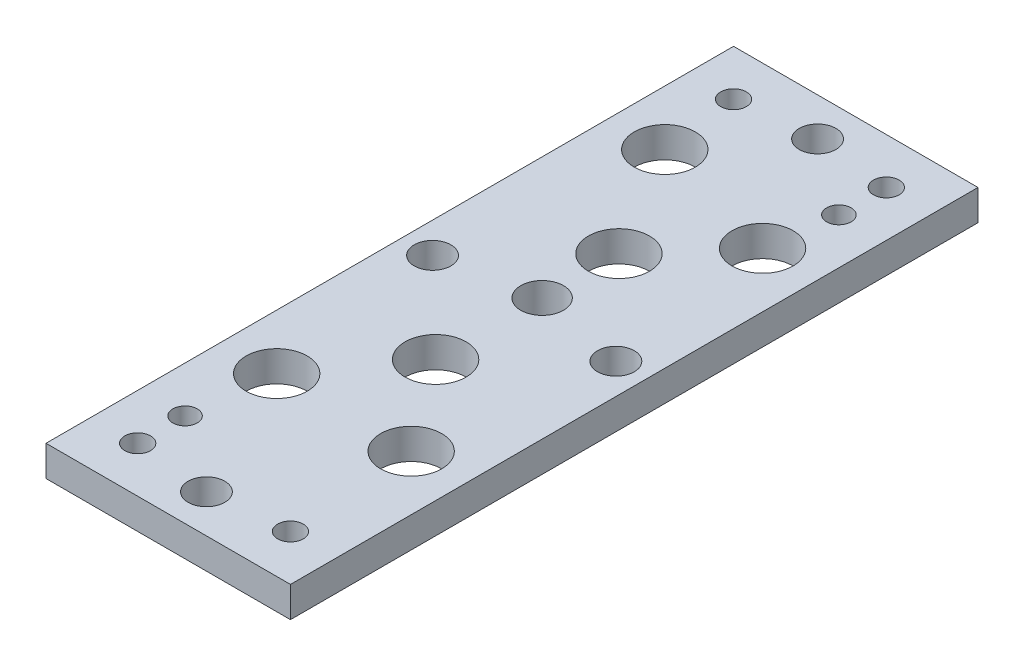
SolidWorks part; units mm, degrees
material "K110"
ref_plane "Front Plane" through (0, 0, 0) normal (0, 0, 1) x (1, 0, 0)
ref_plane "Top Plane" through (0, 0, 0) normal (0, 1, 0) x (1, 0, 0)
ref_plane "Right Plane" through (0, 0, 0) normal (1, 0, 0) x (0, 0, -1)
sketch "Sketch1" plane through (0, 0, 0) normal (0, 1, 0) x (1, 0, 0)
  line L1 (-40, -112.5) -> (40, -112.5)
  line L2 (-40, -112.5) -> (-40, 112.5)
  line L3 (-40, 112.5) -> (40, 112.5)
  line L4 (40, -112.5) -> (40, 112.5)
  line L5 (-40, -112.5) -> (40, 112.5) construction
  line L6 (-40, 112.5) -> (40, -112.5) construction
  point P0 (0, 0)
  dimension "D1" = 225
  dimension "D2" = 80
extrude "Boss-Extrude1" add sketch "Sketch1" against normal blind 10
sketch "Sketch2" plane through (0, 0, 0) normal (0, 1, 0) x (1, 0, 0)
  circle A0 centre (0, 100) radius 6 construction
  circle A1 centre (30, 4) radius 6 construction
  circle A2 centre (-30, 4) radius 6 construction
  circle A3 centre (0, -100) radius 6 construction
  circle A4 centre (0, 100) radius 6
  circle A5 centre (30, 4) radius 6
  circle A6 centre (-30, 4) radius 6
  circle A7 centre (0, -100) radius 6
extrude "Cut-Extrude1" cut sketch "Sketch2" against normal up to next
hole_wizard "M8 Clearance Hole1" positions "Sketch6" profile "Sketch5" hole size "M8" standard "ISO" end condition through all
sketch "Sketch6" plane through (0, 0, 0) normal (0, 1, 0) x (1, 0, 0)
  point P0 (-25, 97.5)
  point P3 (25, 97.5)
  point P6 (25, -97.5)
  point P9 (-25, -97.5)
sketch "Sketch5" plane through (-25, 0, -97.5) normal (1, 0, 0) x (0, 0, 1)
  line L0 (0, 0) -> (0, 10)
  line L1 (0, 10) -> (4.2, 10)
  line L2 (4.2, 10) -> (4.2, 0)
  line L5 (4.2, 0) -> (0, 0)
  line L11 (0, -6.35) -> (0, 107.95) construction
  dimension "Thru Hole Dia." = 8.4
  dimension "Thru Hole Depth" = 10
hole_wizard "Ø8.0mm Dowel Hole1" positions "Sketch9" profile "Sketch8" hole size "Ø8.0" standard "ISO" end condition through all
sketch "Sketch9" plane through (0, 0, 0) normal (0, 1, 0) x (1, 0, 0)
  point P0 (25, 81.975)
  point P3 (-25, -82)
sketch "Sketch8" plane through (25, 0, -81.975) normal (1, 0, 0) x (0, 0, 1)
  line L0 (0, 0) -> (0, 10)
  line L1 (0, 10) -> (4, 10)
  line L2 (4, 10) -> (4, 0)
  line L5 (4, 0) -> (0, 0)
  line L11 (0, -6.35) -> (0, 107.95) construction
  dimension "Thru Hole Dia." = 8
  dimension "Thru Hole Depth" = 10
sketch "Sketch10" plane through (0, 0, 0) normal (0, 1, 0) x (1, 0, 0)
  circle A0 centre (0, 9.86) radius 7 construction
  circle A1 centre (0, 9.86) radius 7
extrude "Cut-Extrude3" cut sketch "Sketch10" against normal up to next
sketch "Sketch14" plane through (0, -10, 0) normal (0, 1, 0) x (1, 0, 0)
  circle A0 centre (22, 60) radius 10 construction
  circle A1 centre (-22, 72) radius 10 construction
  circle A2 centre (0, 35) radius 10 construction
  circle A3 centre (0, -25) radius 10 construction
  circle A4 centre (-22, -55) radius 10 construction
  circle A5 centre (22, -55) radius 10 construction
  circle A6 centre (22, 60) radius 10
  circle A7 centre (-22, 72) radius 10
  circle A8 centre (0, 35) radius 10
  circle A9 centre (0, -25) radius 10
  circle A10 centre (-22, -55) radius 10
  circle A11 centre (22, -55) radius 10
extrude "Cut-Extrude4" cut sketch "Sketch14" along normal through all
